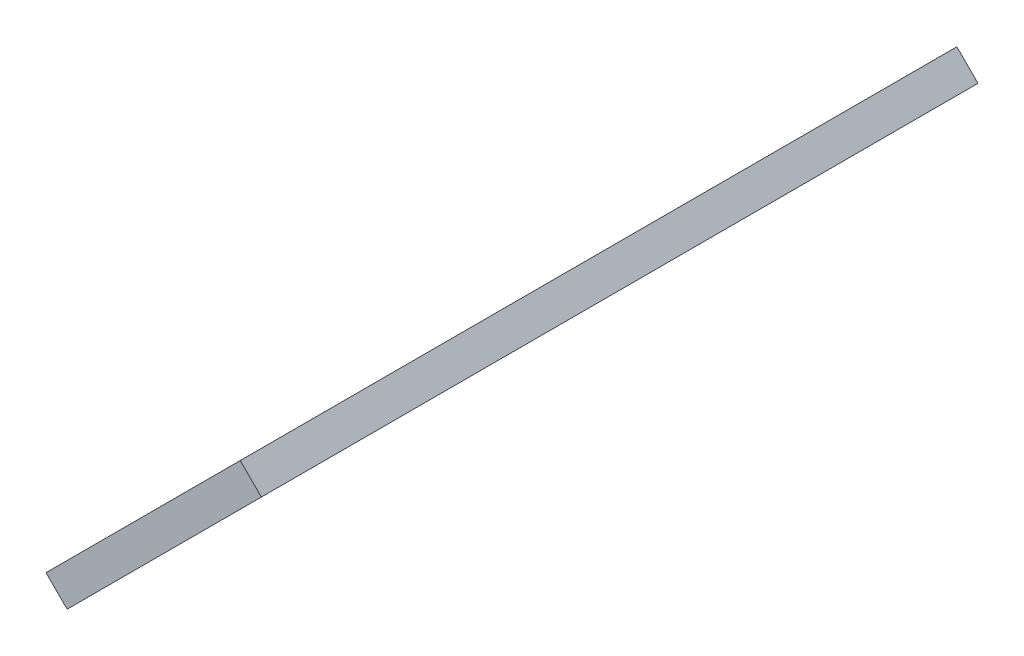
SolidWorks part; units mm, degrees
ref_plane "Front Plane" through (0, 0, 0) normal (0, 0, 1) x (1, 0, 0)
ref_plane "Top Plane" through (0, 0, 0) normal (0, 1, 0) x (1, 0, 0)
ref_plane "Right Plane" through (0, 0, 0) normal (1, 0, 0) x (0, 0, -1)
sketch "Sketch1" plane through (0, 0, 0) normal (0, 0, 1) x (1, 0, 0)
  line L0 (-108.2121, 4.5408) -> (-66.9029, 45.85)
  line L1 (-108.2121, 4.5408) -> (-112.7022, 9.0309)
  line L2 (-66.9029, 45.85) -> (-71.393, 50.3401)
  line L3 (-112.7022, 9.0309) -> (-71.393, 50.3401)
  line L4 (-76.7812, -26.8901) -> (-72.2911, -22.4) construction
extrude "Boss-Extrude1" add sketch "Sketch1" along normal up to surface (152.4 mm away)
